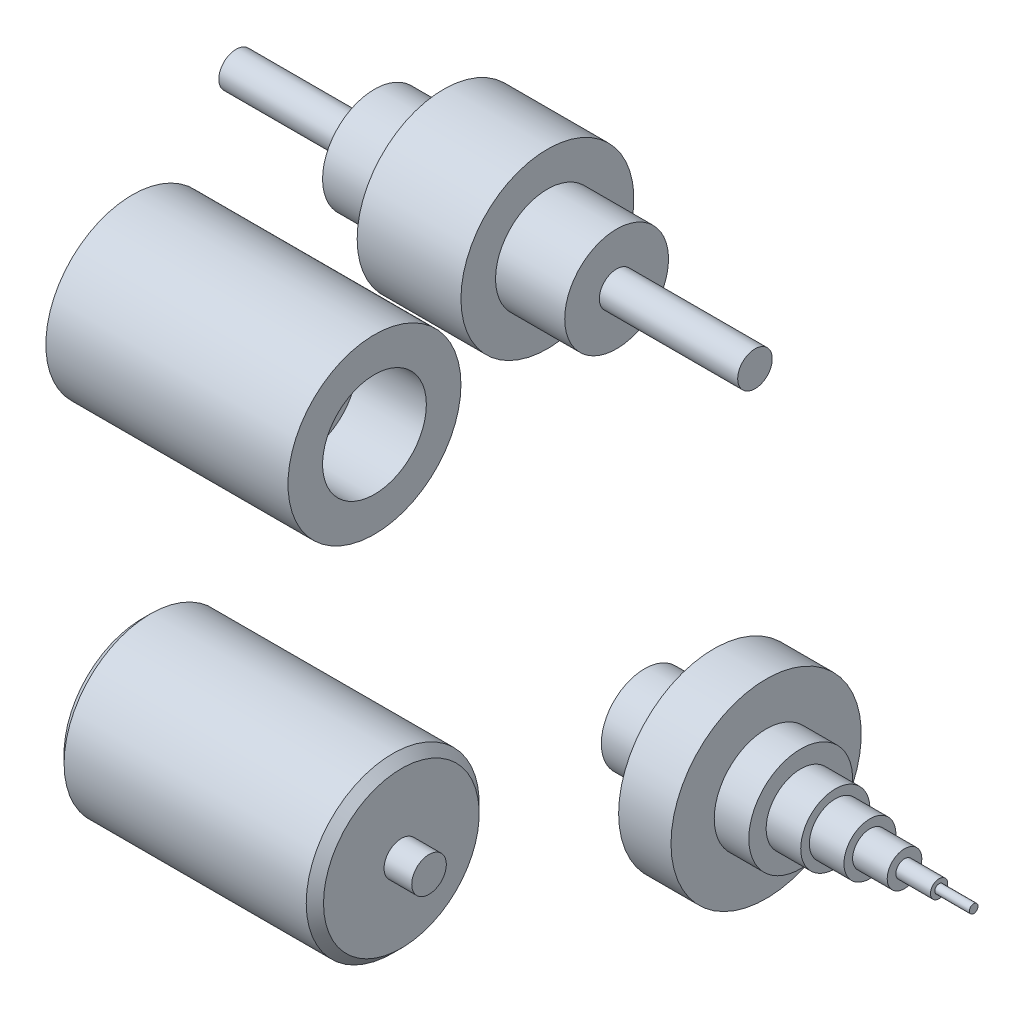
SolidWorks part; units mm, degrees
ref_plane "Alzado" through (0, 0, 0) normal (0, 0, 1) x (1, 0, 0)
ref_plane "Planta" through (0, 0, 0) normal (0, 1, 0) x (1, 0, 0)
ref_plane "Vista lateral" through (0, 0, 0) normal (1, 0, 0) x (0, 0, -1)
sketch "Croquis2" plane through (0, 0, 0) normal (0, 0, 1) x (1, 0, 0)
  line L12 (-16.1177, -67.9976) -> (283.8823, -67.9976)
  line L13 (283.8823, -67.9976) -> (283.8823, -57.9976)
  line L14 (283.8823, -57.9976) -> (203.8823, -57.9976)
  line L15 (203.8823, -57.9976) -> (203.8823, -37.9976)
  line L16 (203.8823, -37.9976) -> (163.8823, -37.9976)
  line L17 (163.8823, -37.9976) -> (163.8823, -17.9976)
  line L18 (163.8823, -17.9976) -> (103.8823, -17.9976)
  line L19 (103.8823, -17.9976) -> (103.8823, -37.9976)
  line L20 (103.8823, -37.9976) -> (63.8823, -37.9976)
  line L21 (63.8823, -37.9976) -> (63.8823, -57.9976)
  line L22 (63.8823, -57.9976) -> (-16.1177, -57.9976)
  line L23 (-16.1177, -57.9976) -> (-16.1177, -67.9976)
  line L24 (-16.1177, -67.9976) -> (-83.7964, -67.9976)
  line L25 (-83.7964, -67.9976) -> (364.2473, -67.9976)
  line L30 (-56.1177, -210.8672) -> (-56.1177, -220.8672)
  line L31 (-56.1177, -220.8672) -> (23.8823, -220.8672)
  line L32 (23.8823, -220.8672) -> (23.8823, -240.8672)
  line L33 (23.8823, -240.8672) -> (63.8823, -240.8672)
  line L34 (63.8823, -240.8672) -> (63.8823, -260.8672)
  line L35 (63.8823, -260.8672) -> (-76.1177, -260.8672)
  line L36 (-76.1177, -260.8672) -> (-76.1177, -210.8672)
  line L38 (63.8823, -180.8672) -> (63.8823, -240.8672) construction
  line L39 (-76.1177, -210.8672) -> (-56.1177, -210.8672)
  line L40 (101.4708, -210.8672) -> (-129.3819, -210.8672) construction
  dimension "D1" = 40
  dimension "D2" = 40
  dimension "D3" = 80
  dimension "D4" = 80
  dimension "D5" = 300
  dimension "D6" = 10
  dimension "D7" = 30
  dimension "D8" = 50
  dimension "D9" = 10
  dimension "D10" = 30
  dimension "D11" = 20
  dimension "D14" = 20
  dimension "D19" = 120
  dimension "D20" = 40
revolve "Revolución2" add sketch "Croquis2" angle 360 about L25
revolve "Revolución4" add sketch "Croquis2<13>" angle 360 about L40 region at (-16.5177, -241.4672, 0)
sketch "Croquis2<13>" plane through (0, 0, 0) normal (0, 0, 1) x (1, 0, 0) same geometry as "Croquis2"
sketch "Croquis3" plane through (0, 0, 0) normal (0, 0, 1) x (1, 0, 0)
  line L0 (141.0761, -275.0792) -> (410.3294, -275.0792) construction
  line L1 (410.3294, -275.0792) -> (410.3294, -277.5792)
  line L2 (410.3294, -277.5792) -> (390.3294, -277.5792)
  line L3 (390.3294, -277.5792) -> (390.3294, -280.0792)
  line L4 (390.3294, -280.0792) -> (370.3294, -280.0792)
  line L5 (370.3294, -280.0792) -> (370.3294, -285.0792)
  line L6 (370.3294, -285.0792) -> (350.3294, -285.0792)
  line L7 (350.3294, -285.0792) -> (350.3294, -290.0792)
  line L8 (350.3294, -290.0792) -> (330.3294, -290.0792)
  line L9 (330.3294, -290.0792) -> (330.3294, -295.0792)
  line L10 (330.3294, -295.0792) -> (310.3294, -295.0792)
  line L11 (310.3294, -295.0792) -> (310.3294, -305.0792)
  line L12 (310.3294, -305.0792) -> (290.3294, -305.0792)
  line L13 (260.0483, -330.0792) -> (260.0483, -300.0792)
  line L14 (260.0483, -300.0792) -> (220.0483, -300.0792)
  line L15 (220.0483, -300.0792) -> (220.0483, -275.0792)
  line L16 (290.3294, -305.0792) -> (290.3294, -330.0792)
  line L17 (290.3294, -330.0792) -> (260.0483, -330.0792)
  line L18 (410.3294, -275.0792) -> (220.0483, -275.0792)
  point P2 (310.3294, -300.0792)
  point P20 (260.0483, -315.0792)
  dimension "D1" = 40
  dimension "D2" = 20
  dimension "D3" = 20
  dimension "D4" = 20
  dimension "D5" = 20
  dimension "D6" = 20
  dimension "D7" = 2.5
  dimension "D8" = 5
  dimension "D9" = 10
  dimension "D10" = 15
  dimension "D11" = 20
  dimension "D12" = 25
  dimension "D13" = 20
  dimension "D14" = 25
  dimension "D15" = 40
revolve "Revolución5" add sketch "Croquis3" angle 360 about L0
sketch "Croquis5" plane through (220.0483, 0, 0) normal (-1, 0, 0) x (0, 0, 1)
  circle A0 centre (0, -275.0792) radius 20
extrude "Cortar-Extruir1" cut sketch "Croquis5" against normal blind 43 contours A0
sketch "Croquis6" plane through (0, 0, 0) normal (0, 0, 1) x (1, 0, 0)
  line L0 (-86.5717, -415.363) -> (-86.5717, -405.363)
  line L1 (-86.5717, -405.363) -> (-70.5717, -405.363)
  line L2 (-70.5717, -405.363) -> (-70.5717, -365.363)
  line L3 (-70.5717, -365.363) -> (79.4283, -365.363)
  line L4 (79.4283, -365.363) -> (79.4283, -405.363)
  line L5 (79.4283, -405.363) -> (95.4283, -405.363)
  line L6 (95.4283, -405.363) -> (95.4283, -415.363)
  line L12 (-86.5717, -415.363) -> (95.4283, -415.363)
  line L13 (-110.3904, -415.363) -> (135.5249, -415.363) construction
  dimension "D1" = 182
  dimension "D2" = 10
  dimension "D3" = 150
  dimension "D4" = 40
  dimension "D5" = 16
revolve "Revolución6" add sketch "Croquis6" angle 360 about L13
chamfer "Chaflán1" distance 5 angle 45 1 edges at (-70.5717, -415.363, 50)
chamfer "Chaflán2" distance 5 angle 45 1 edges at (79.4283, -415.363, 50)
